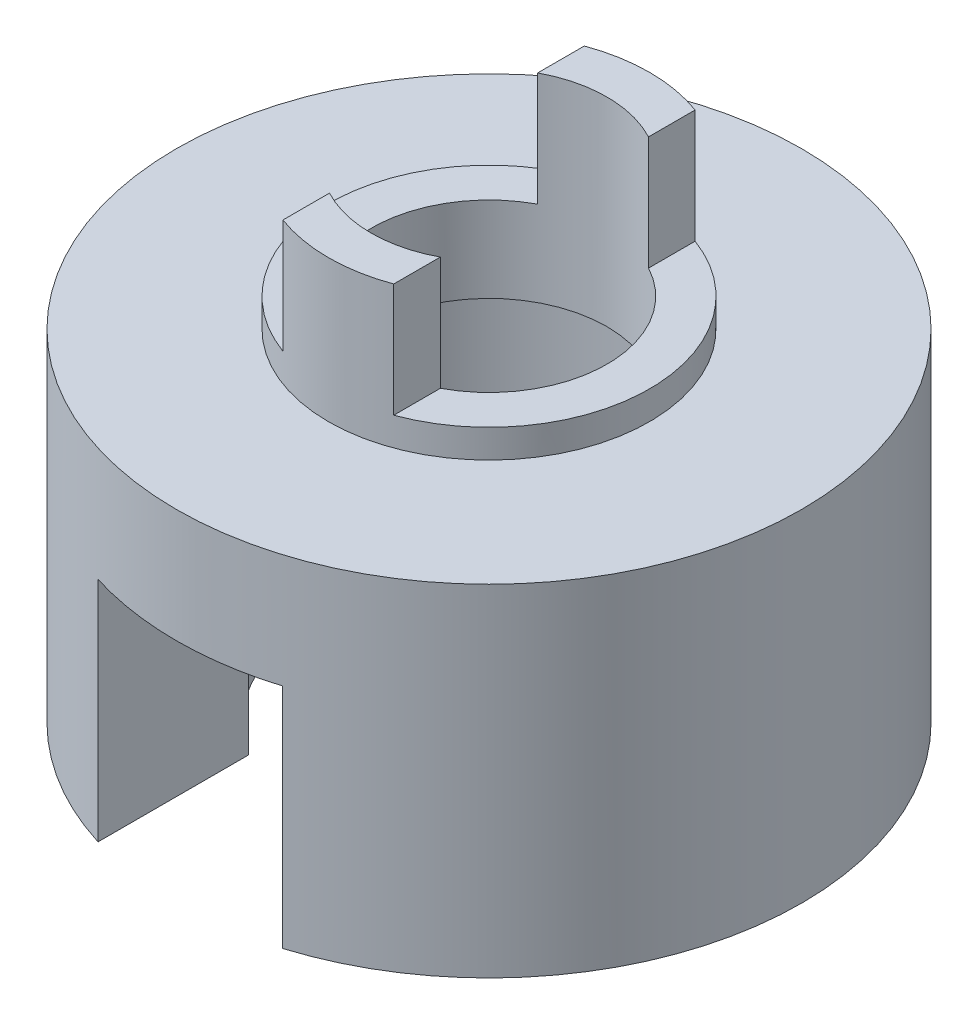
SolidWorks part; units mm, degrees
other "标注1"
sketch "草图3" plane through (-11, 9, 11) normal (-0.0956, 0.99, 0.1036) x (0.8293, 0.1368, -0.5418)
ref_plane "前视基准面" through (0, 0, 0) normal (0, 0, 1) x (1, 0, 0)
ref_plane "上视基准面" through (0, 0, 0) normal (0, 1, 0) x (1, 0, 0)
ref_plane "右视基准面" through (0, 0, 0) normal (1, 0, 0) x (0, 0, -1)
sketch "草图1" plane through (0, 0, 0) normal (0, 1, 0) x (1, 0, 0)
  circle A1 centre (0, 0) radius 5.65
  circle A2 centre (0, 0) radius 11
  circle A3 centre (0, 0) radius 4.15
  dimension "D1" = 11.3
  dimension "D2" = 22
  dimension "D3" = 1.5
extrude "凸台-拉伸1" add sketch "草图1" against normal blind 2 contours A2 | A3
extrude "凸台-拉伸2" add sketch "草图1<3>" along normal blind 5 contours A1 A3 region at (-5.4902, 0, 0)
sketch "草图1<3>" plane through (0, 0, 0) normal (0, 1, 0) x (1, 0, 0) same geometry as "草图1"
sketch "草图2" plane through (0, 5, 0) normal (0, 1, 0) x (1, 0, 0)
  line L0 (0, 0) -> (0, 50000) construction
  line L1 (1.95, 5.3028) -> (1.95, 3.6633)
  line L2 (-1.95, 5.3028) -> (-1.95, 3.6633)
  line L3 (1.95, -3.6633) -> (1.95, -5.3028)
  line L4 (-1.95, -3.6633) -> (-1.95, -5.3028)
  circle A1 centre (0, 0) radius 4.15 construction
  arc A3 (-1.95, 3.6633) -> (-1.95, -3.6633) centre (0, 0) ccw
  circle A4 centre (0, 0) radius 5.65 construction
  arc A5 (-1.95, 5.3028) -> (-1.95, -5.3028) centre (0, 0) ccw
  arc A6 (0, 5.65) -> (-1.95, 5.3028) centre (0, 0) ccw construction
  arc A7 (0, 4.15) -> (-1.95, 3.6633) centre (0, 0) ccw construction
  arc A8 (1.95, 5.3028) -> (0, 5.65) centre (0, 0) ccw construction
  arc A9 (1.95, 3.6633) -> (0, 4.15) centre (0, 0) ccw construction
  arc A10 (-1.95, -3.6633) -> (0, -4.15) centre (0, 0) ccw construction
  arc A11 (1.95, -3.6633) -> (1.95, 3.6633) centre (0, 0) ccw
  arc A12 (-1.95, -5.3028) -> (0, -5.65) centre (0, 0) ccw construction
  arc A13 (1.95, -5.3028) -> (1.95, 5.3028) centre (0, 0) ccw
  arc A14 (0, -4.15) -> (1.95, -3.6633) centre (0, 0) ccw construction
  arc A15 (0, -5.65) -> (1.95, -5.3028) centre (0, 0) ccw construction
  dimension "D1" = 1.95
extrude "切除-拉伸1" cut sketch "草图2" against normal blind 4
sketch "草图4" plane through (0, -2, 0) normal (0, -1, 0) x (1, 0, 0)
  circle A0 centre (0, 0) radius 6.15
  circle A1 centre (0, 0) radius 11
  dimension "D1" = 12.3
extrude "凸台-拉伸3" add sketch "草图4" along normal blind 10
sketch "草图5" plane through (0, -12, 0) normal (0, -1, 0) x (1, 0, 0)
  line L0 (-11.1812, 2.5) -> (-5.6189, 2.5)
  line L1 (-11.1812, -2.5) -> (-5.6189, -2.5)
  line L2 (-5.6189, 2.5) -> (-5.6189, -2.5)
  line L3 (-5.6189, 0) -> (-6.15, 0) construction
  line L4 (-11.1812, 2.5) -> (-11.1812, -2.5)
  line L5 (0, 11) -> (0, 6.15) construction
  line L6 (-3.25, 5.2211) -> (-3.25, 12.1516)
  line L7 (-3.25, 12.1516) -> (3.25, 12.1516)
  line L8 (3.25, 12.1516) -> (3.25, 5.2211)
  line L9 (-3.25, 5.2211) -> (3.25, 5.2211)
  circle A3 centre (0, 0) radius 6.15 construction
  circle A4 centre (0, 0) radius 6.15 construction
  circle A5 centre (0, 0) radius 11 construction
  point P18 (0, 5.2211)
  circle M6 centre (0, 0) radius 11
  circle M7 centre (0, 0) radius 6.15
  dimension "D1" = 5
  dimension "D2" = 5.5623
  dimension "D3" = 6.5
  dimension "D4" = 6.9305
extrude "切除-拉伸2" cut sketch "草图5" against normal blind 8 contours L8 L6 M6 M7 | L4 L1 L2 L0 region at (0, -12, 8.3387)
